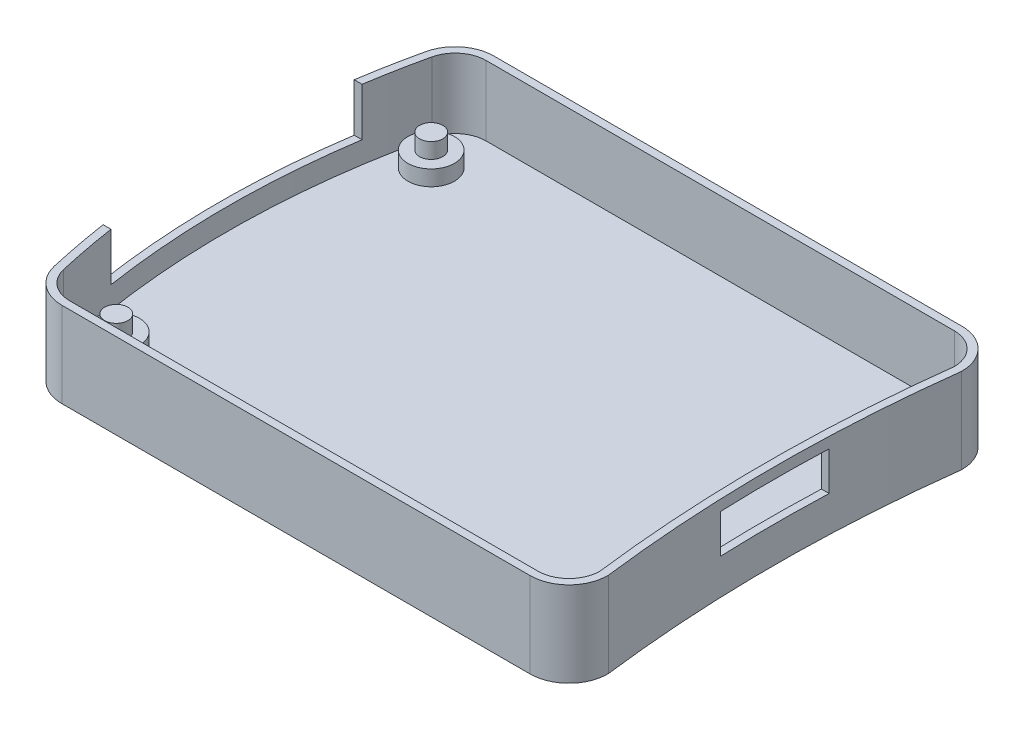
SolidWorks part; units mm, degrees
ref_plane "Front Plane" through (0, 0, 0) normal (0, 0, 1) x (1, 0, 0)
ref_plane "Top Plane" through (0, 0, 0) normal (0, 1, 0) x (1, 0, 0)
ref_plane "Right Plane" through (0, 0, 0) normal (1, 0, 0) x (0, 0, -1)
sketch "Sketch1" plane through (0, 0, 0) normal (0, 1, 0) x (1, 0, 0)
  line L0 (0, 20.2635) -> (0, -20.6983) construction
  line L1 (-48.5386, 0) -> (50.9036, 0) construction
  line L2 (-36.322, 3.1321) -> (-36.322, 0) construction
  line L3 (30.48, 26.67) -> (-38.692, 26.67) construction
  line L4 (32.868, 0.8812) -> (32.868, 0) construction
  line L5 (30.48, 26.67) -> (-29.9413, 26.67)
  line L6 (30.48, -26.67) -> (-29.9413, -26.67)
  circle A0 centre (30.48, 22.86) radius 1.6
  circle A1 centre (30.48, 22.86) radius 3.81 construction
  circle A2 centre (-30.48, 20.32) radius 1.6
  circle A3 centre (-30.48, 20.32) radius 3.81 construction
  arc A4 (34.29, -22.86) -> (34.29, 22.86) centre (217.3271, 0) cw
  arc A5 (-33.6457, -23.7168) -> (-33.6457, 23.7168) centre (70.104, 0) cw
  arc A6 (-33.6457, 23.7168) -> (-29.9413, 26.67) centre (-29.9413, 22.87) cw
  arc A7 (30.48, 26.67) -> (34.29, 22.86) centre (30.48, 22.86) cw
  circle A8 centre (30.48, -22.86) radius 1.6
  arc A9 (30.48, -26.67) -> (34.29, -22.86) centre (30.48, -22.86) ccw
  circle A10 centre (30.48, -22.86) radius 3.81 construction
  circle A11 centre (-30.48, -20.32) radius 3.81 construction
  circle A12 centre (-30.48, -20.32) radius 1.6
  arc A13 (-33.6457, -23.7168) -> (-29.9413, -26.67) centre (-29.9413, -22.87) ccw
  point P21 (-32.9261, 26.67)
  dimension "D1" = 3.2
  dimension "D4" = 7.62
  dimension "D6" = 3.2
  dimension "D8" = 7.62
  dimension "D11" = 3.8
  dimension "D2" = 22.86
  dimension "D3" = 30.48
  dimension "D5" = 30.48
  dimension "D7" = 40.64
  dimension "D9" = 2.388
  dimension "D10" = 70.612
sketch "Sketch7" plane through (0, 0, 0) normal (0, 1, 0) x (1, 0, 0)
  line L4 (30.48, 27.87) -> (-29.9413, 27.87)
  line L5 (-29.9413, -27.87) -> (30.48, -27.87)
  line L6 (30.48, 27.87) -> (-29.9413, 27.87)
  line L7 (-29.9413, -27.87) -> (30.48, -27.87)
  arc A12 (-29.9413, 27.87) -> (-34.8156, 23.9842) centre (-29.9413, 22.87) ccw
  arc A13 (-34.8156, 23.9842) -> (-34.8156, -23.9842) centre (70.104, 0) ccw
  arc A14 (-34.8156, -23.9842) -> (-29.9413, -27.87) centre (-29.9413, -22.87) ccw
  arc A15 (30.48, -27.87) -> (35.4894, -22.7802) centre (30.48, -22.86) ccw
  arc A16 (35.4894, 22.7802) -> (35.4894, -22.7802) centre (217.3271, 0) ccw
  arc A17 (35.4894, 22.7802) -> (30.48, 27.87) centre (30.48, 22.86) ccw
  arc A18 (-29.9413, 27.87) -> (-34.8156, 23.9842) centre (-29.9413, 22.87) ccw
  arc A19 (-34.8156, 23.9842) -> (-34.8156, -23.9842) centre (70.104, 0) ccw
  arc A20 (-34.8156, -23.9842) -> (-29.9413, -27.87) centre (-29.9413, -22.87) ccw
  arc A21 (30.48, -27.87) -> (35.4894, -22.7802) centre (30.48, -22.86) ccw
  arc A22 (35.4894, 22.7802) -> (35.4894, -22.7802) centre (217.3271, 0) ccw
  arc A23 (35.4894, 22.7802) -> (30.48, 27.87) centre (30.48, 22.86) ccw
  dimension "D1" = 1.2
extrude "Boss-Extrude7" add sketch "Sketch7" along normal blind 2
sketch "Sketch8" plane through (0, 2, 0) normal (0, 1, 0) x (1, 0, 0)
  circle A0 centre (-30.48, 20.32) radius 3
  circle A1 centre (-30.48, -20.32) radius 3
  circle A2 centre (30.48, -22.86) radius 3
  circle A3 centre (30.48, 22.86) radius 3
  circle A4 centre (-30.48, -20.32) radius 1.6 construction
  dimension "D1" = 6
extrude "Boss-Extrude8" add sketch "Sketch8" along normal blind 2
sketch "Sketch9" plane through (0, 4, 0) normal (0, 1, 0) x (1, 0, 0)
  circle A0 centre (-30.48, 20.32) radius 1.5
  circle A1 centre (30.48, 22.86) radius 1.5
  circle A2 centre (30.48, -22.86) radius 1.5
  circle A3 centre (-30.48, -20.32) radius 1.5
  dimension "D1" = 3
extrude "Boss-Extrude9" add sketch "Sketch9" along normal blind 2
sketch "Sketch10" plane through (0, 2, 0) normal (0, 1, 0) x (1, 0, 0)
  line L12 (30.48, 27.87) -> (-29.9413, 27.87)
  line L13 (-29.9413, -27.87) -> (30.48, -27.87)
  line L14 (-29.9413, -26.87) -> (30.48, -26.87)
  line L15 (30.48, 26.87) -> (-29.9413, 26.87)
  line L16 (-29.9413, -26.87) -> (30.48, -26.87)
  line L17 (30.48, 26.87) -> (-29.9413, 26.87)
  arc A24 (35.4894, 22.7802) -> (30.48, 27.87) centre (30.48, 22.86) ccw
  arc A25 (-29.9413, 27.87) -> (-34.8156, 23.9842) centre (-29.9413, 22.87) ccw
  arc A26 (-34.8156, 23.9842) -> (-34.8156, -23.9842) centre (70.104, 0) ccw
  arc A27 (-34.8156, -23.9842) -> (-29.9413, -27.87) centre (-29.9413, -22.87) ccw
  arc A28 (30.48, -27.87) -> (35.4894, -22.7802) centre (30.48, -22.86) ccw
  arc A29 (35.4894, 22.7802) -> (35.4894, -22.7802) centre (217.3271, 0) ccw
  arc A30 (34.49, 22.8474) -> (30.48, 26.87) centre (30.48, 22.86) ccw
  arc A31 (34.49, 22.8474) -> (34.49, -22.8474) centre (217.3271, 0) ccw
  arc A32 (30.48, -26.87) -> (34.49, -22.8474) centre (30.48, -22.86) ccw
  arc A33 (-33.8407, -23.7614) -> (-29.9413, -26.87) centre (-29.9413, -22.87) ccw
  arc A34 (-33.8407, 23.7614) -> (-33.8407, -23.7614) centre (70.104, 0) ccw
  arc A35 (-29.9413, 26.87) -> (-33.8407, 23.7614) centre (-29.9413, 22.87) ccw
  arc A36 (34.49, 22.8474) -> (30.48, 26.87) centre (30.48, 22.86) ccw
  arc A37 (34.49, 22.8474) -> (34.49, -22.8474) centre (217.3271, 0) ccw
  arc A38 (30.48, -26.87) -> (34.49, -22.8474) centre (30.48, -22.86) ccw
  arc A39 (-33.8407, -23.7614) -> (-29.9413, -26.87) centre (-29.9413, -22.87) ccw
  arc A40 (-33.8407, 23.7614) -> (-33.8407, -23.7614) centre (70.104, 0) ccw
  arc A41 (-29.9413, 26.87) -> (-33.8407, 23.7614) centre (-29.9413, 22.87) ccw
  dimension "D1" = 1
  dimension "D2" = 1
extrude "Boss-Extrude10" add sketch "Sketch10" along normal blind 9
ref_plane "Plane2" through (34.068, 0, 0) normal (1, 0, 0) x (0, 0, -1)
sketch "Sketch12" plane through (34.068, 0, 0) normal (1, 0, 0) x (0, 0, -1)
  line L0 (0, 15.2062) -> (0, -7.4799) construction
  line L1 (23.7168, 0) -> (-23.7168, 0) construction
  line L2 (-7, 9.6) -> (7, 9.6)
  line L3 (-7, 9.6) -> (-7, 4.6)
  line L4 (-7, 4.6) -> (7, 4.6)
  line L5 (7, 9.6) -> (7, 4.6)
  line L6 (-7, 9.6) -> (7, 4.6) construction
  line L7 (-7, 4.6) -> (7, 9.6) construction
  point P3 (0, 7.1)
  dimension "D1" = 4.6
  dimension "D2" = 14
  dimension "D3" = 5
extrude "Cut-Extrude5" cut sketch "Sketch12" against normal blind 10 and the other way blind 10
sketch "Sketch13" plane through (0, 11, 0) normal (0, 1, 0) x (1, 0, 0)
  line L0 (-48.5386, 0) -> (50.9036, 0) construction
  line L1 (-41.3949, -16.2) -> (-32.665, -16.2)
  line L2 (-41.3949, -16.2) -> (-41.3949, 16.2)
  line L3 (-41.3949, 16.2) -> (-32.665, 16.2)
  line L4 (-32.665, -16.2) -> (-32.665, 16.2)
  line L5 (-41.3949, -16.2) -> (-32.665, 16.2) construction
  line L6 (-41.3949, 16.2) -> (-32.665, -16.2) construction
  point P0 (-37.03, 0)
  dimension "D1" = 32.4
extrude "Cut-Extrude6" cut sketch "Sketch13" against normal offset from surface (6.2 mm away) 2.8 up to face at (-30.48, 2, -17.32)
